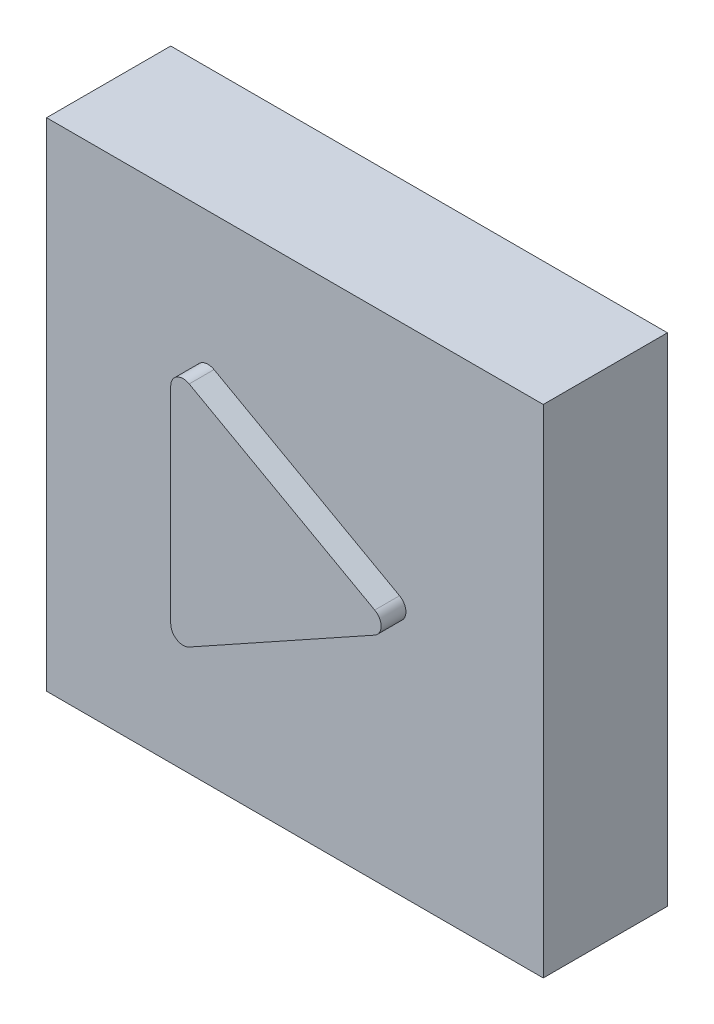
SolidWorks part; units mm, degrees
ref_plane "Front Plane" through (0, 0, 0) normal (0, 0, 1) x (1, 0, 0)
ref_plane "Top Plane" through (0, 0, 0) normal (0, 1, 0) x (1, 0, 0)
ref_plane "Right Plane" through (0, 0, 0) normal (1, 0, 0) x (0, 0, -1)
sketch "Sketch1" plane through (0, 0, 0) normal (0, 0, 1) x (1, 0, 0)
  line L1 (-10, -10) -> (10, -10)
  line L2 (-10, -10) -> (-10, 10)
  line L3 (-10, 10) -> (10, 10)
  line L4 (10, -10) -> (10, 10)
  line L5 (-10, -10) -> (10, 10) construction
  line L6 (-10, 10) -> (10, -10) construction
  point P0 (0, 0)
extrude "Boss-Extrude1" add sketch "Sketch1" along normal blind 5
ref_plane "Plane1" through (0, 0, 5) normal (0, 0, 1) x (1, 0, 0)
sketch "Sketch2" plane through (0, 0, 5) normal (0, 0, 1) x (1, 0, 0)
  line L0 (-4, 4.1502) -> (-4, -4.1502)
  line L1 (-3.2572, -4.5873) -> (4.2133, -0.4371)
  line L2 (4.2133, 0.4371) -> (-3.2572, 4.5873)
  arc A0 (4.2133, -0.4371) -> (4.2133, 0.4371) centre (3.9704, 0) ccw
  arc A1 (-3.2572, -4.5873) -> (-4, -4.1502) centre (-3.5, -4.1502) cw
  arc A2 (-4, 4.1502) -> (-3.2572, 4.5873) centre (-3.5, 4.1502) cw
  dimension "D1" = 0.5
sketch "Sketch4" plane through (0, 0, 5) normal (0, 0, 1) x (1, 0, 0)
  line L1 (-3, 1) -> (2, 1)
  line L2 (-3, 1) -> (-3, -1)
  line L3 (-3, -1) -> (2, -1)
  line L4 (2, 1) -> (2, -1)
sketch "Sketch6" plane through (0, 0, 5) normal (0, 0, 1) x (1, 0, 0)
  circle A0 centre (0, 0) radius 0.75
  circle A1 centre (0, 0) radius 1
extrude "Cut-Extrude1" cut sketch "Sketch6" against normal blind 5 contours A0
extrude "Boss-Extrude2" add sketch "Sketch2" along normal blind 1
